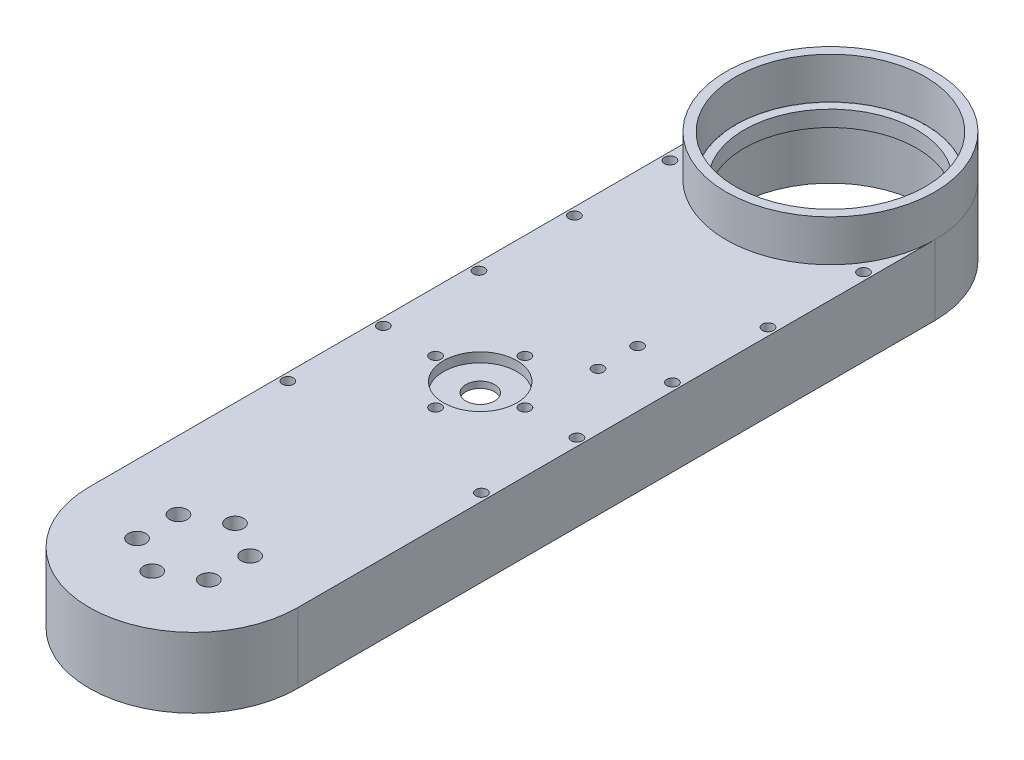
SolidWorks part; units mm, degrees
ref_plane "Front Plane" through (0, 0, 0) normal (0, 0, 1) x (1, 0, 0)
ref_plane "Top Plane" through (0, 0, 0) normal (0, 1, 0) x (1, 0, 0)
ref_plane "Right Plane" through (0, 0, 0) normal (1, 0, 0) x (0, 0, -1)
sketch "Sketch1" plane through (0, 0, 0) normal (0, 1, 0) x (1, 0, 0)
  line L5 (-32.774, -22.3805) -> (-32.774, 177.6195)
  line L6 (32.774, -22.3805) -> (32.774, 177.6195)
  circle A3 centre (0, 177.6195) radius 4.5
  circle A4 centre (0, 67.6378) radius 4.5
  circle A5 centre (15, 89.6378) radius 1.75
  circle A7 centre (-6.7334, 37.1195) radius 1.25
  circle A8 centre (-6.7334, 27.6195) radius 1.25
  circle A14 centre (0, 53.6052) radius 1.75
  circle A15 centre (-14.0327, 67.6378) radius 1.75
  circle A16 centre (0, 81.6705) radius 1.75
  circle A17 centre (14.0327, 67.6378) radius 1.75
  circle A18 centre (0, 67.6378) radius 11.5
  circle A19 centre (0, 67.6378) radius 4.5
  arc A22 (32.774, -22.3805) -> (-32.774, -22.3805) centre (0, -22.3805) cw
  arc A23 (32.774, 177.6195) -> (-32.774, 177.6195) centre (0, 177.6195) ccw
  circle A25 centre (0, -9.3805) radius 2.75
  circle A27 centre (11.2583, -15.8805) radius 2.75
  circle A28 centre (11.2583, -28.8805) radius 2.75
  circle A29 centre (0, -35.3805) radius 2.75
  circle A30 centre (-11.2583, -28.8805) radius 2.75
  circle A31 centre (-11.2583, -15.8805) radius 2.75
  dimension "D1" = 13
  dimension "D2" = 200
  dimension "D3" = 50
  dimension "D4" = 109.9817
  dimension "D5" = 22
  dimension "D8" = 9.5
  dimension "D6" = 15
extrude "Boss-Extrude10" add sketch "Sketch1" against normal blind 5 contours L6 A23 L5 A22 A31 A30 A29 A28 A27 A25 A3 A5 A7 A8 A14 A15 A16 A17 A18 | A18 | A19 region at (-30.0388, 0, -77.6195)
sketch "Sketch2" plane through (0, 0, 0) normal (0, -1, 0) x (1, 0, 0)
  line L30 (28, -177.6198) -> (28, -97.6193)
  line L35 (-28, -177.6198) -> (-28, -97.62)
  line L46 (-28, -4.769) -> (28, -4.769)
  line L54 (-32.774, 22.3805) -> (-32.774, -177.6198)
  line L55 (32.774, 22.3805) -> (32.774, -177.6198)
  line L56 (-28, 22.3805) -> (-28, -97.62)
  line L57 (28, -97.6193) -> (28, 22.3805)
  circle A4 centre (-18, -157.4003) radius 1.75
  circle A5 centre (18.0605, -157.4003) radius 1.75
  circle A6 centre (-18, -97.6199) radius 1.75
  circle A7 centre (18.0032, -97.4003) radius 1.75
  arc A15 (28, -177.6198) -> (-28, -177.6198) centre (0, -177.6198) cw
  arc A26 (32.774, 22.3805) -> (-32.774, 22.3805) centre (0, 22.3805) ccw
  arc A28 (-32.774, -177.6198) -> (32.774, -177.6198) centre (0, -177.6198) ccw
  arc A29 (28, 22.3805) -> (-28, 22.3805) centre (0, 22.3805) ccw
  dimension "D1" = 60
extrude "Boss-Extrude9" add sketch "Sketch2" along normal blind 22 contours A29 L57 L30 A15 L35 L56 region at (0, 0, 52.4193)
extrude "Cut-Extrude3" cut sketch "Sketch1<14>" against normal blind 3 contours A18 A4 region at (-11.1747, 0, -67.6378)
sketch "Sketch1<14>" plane through (0, 0, 0) normal (0, 1, 0) x (1, 0, 0) same geometry as "Sketch1"
extrude "Boss-Extrude11" add sketch "Sketch1<16>" against normal blind 5 contours A7 | A8 region at (-6.7334, 0, -37.1195) region at (-6.7334, 0, -27.6195)
sketch "Sketch1<16>" plane through (0, 0, 0) normal (0, 1, 0) x (1, 0, 0) same geometry as "Sketch1"
extrude "Boss-Extrude12" add sketch "Sketch2<13>" along normal blind 22 contours L57 A29 L56 region at (0, 0, 20.1987)
sketch "Sketch2<13>" plane through (0, 0, 0) normal (0, -1, 0) x (1, 0, 0) same geometry as "Sketch2"
extrude "Cut-Extrude4" cut sketch "Sketch1<17>" against normal blind 55 contours A30 | A29 | A31 | A25 | A27 | A28 region at (0, 0, 9.3805) region at (11.2583, 0, 15.8805) region at (11.2583, 0, 28.8805) region at (0, 0, 35.3805) region at (-11.2583, 0, 28.8805) region at (-11.2583, 0, 15.8805)
sketch "Sketch1<17>" plane through (0, 0, 0) normal (0, 1, 0) x (1, 0, 0) same geometry as "Sketch1"
sketch "Sketch3" plane through (0, -5, 0) normal (0, -1, 0) x (1, 0, 0)
  line L0 (32.774, 22.3805) -> (32.774, -177.6198) construction
  line L1 (28, -177.6198) -> (28, -4.769) construction
  line L2 (-32.774, 22.3805) -> (-32.774, -177.6198) construction
  circle A0 centre (15, -89.6378) radius 1.75
  circle A4 centre (15, -102.0563) radius 1.75
  circle A6 centre (-30.389, -97.6195) radius 1.75
  circle A7 centre (30.389, -37.6195) radius 1.75
  arc A8 (32.774, 22.3805) -> (-32.774, 22.3805) centre (0, 22.3805) ccw construction
  circle A9 centre (-30.389, -37.6195) radius 1.75
  circle A10 centre (-30.389, -67.6195) radius 1.75
  circle A11 centre (-30.389, -127.6195) radius 1.75
  circle A12 centre (-30.389, -157.6195) radius 1.75
  circle A14 centre (30.389, -157.6195) radius 1.75
  circle A15 centre (30.389, -127.6195) radius 1.75
  circle A16 centre (30.389, -67.6195) radius 1.75
  circle A17 centre (30.389, -97.6195) radius 1.75
  dimension "D1" = 60
  dimension "D6" = 30
  dimension "D4" = 2.385
  dimension "D2" = 2.385
  dimension "D3" = 13
  dimension "D5" = 60
  dimension "D7" = 4
extrude "Cut-Extrude5" cut sketch "Sketch3" against normal blind 21 and the other way blind 79
sketch "Sketch4" plane through (0, -22, 0) normal (0, -1, 0) x (-1, 0, 0)
  arc A0 (32.774, -22.3805) -> (-32.774, -22.3805) centre (0, -22.3805) cw
sketch "Sketch6" plane through (0, -5, 0) normal (0, -1, 0) x (1, 0, 0)
  circle A0 centre (0.006, -177.6195) radius 4.494
sketch "Sketch7" plane through (0, -5, 0) normal (0, -1, 0) x (1, 0, 0)
  circle A0 centre (0, -177.6198) radius 29.72
extrude "Cut-Extrude6" cut sketch "Sketch7" against normal blind 62 and the other way blind 32
sketch "Sketch8" plane through (0, -5, 0) normal (0, -1, 0) x (1, 0, 0)
  circle A0 centre (0.006, -177.6195) radius 27.095
  circle A1 centre (0.006, -177.6195) radius 29.714
extrude "Boss-Extrude13" add sketch "Sketch8" against normal blind 5 separate body
sketch "Sketch9" plane through (0, 0, 0) normal (0, 1, 0) x (1, 0, 0)
  circle A0 centre (0.006, 177.6195) radius 29.85
  circle A1 centre (0.006, 177.6195) radius 32.768
extrude "Boss-Extrude14" add sketch "Sketch9" along normal blind 13
